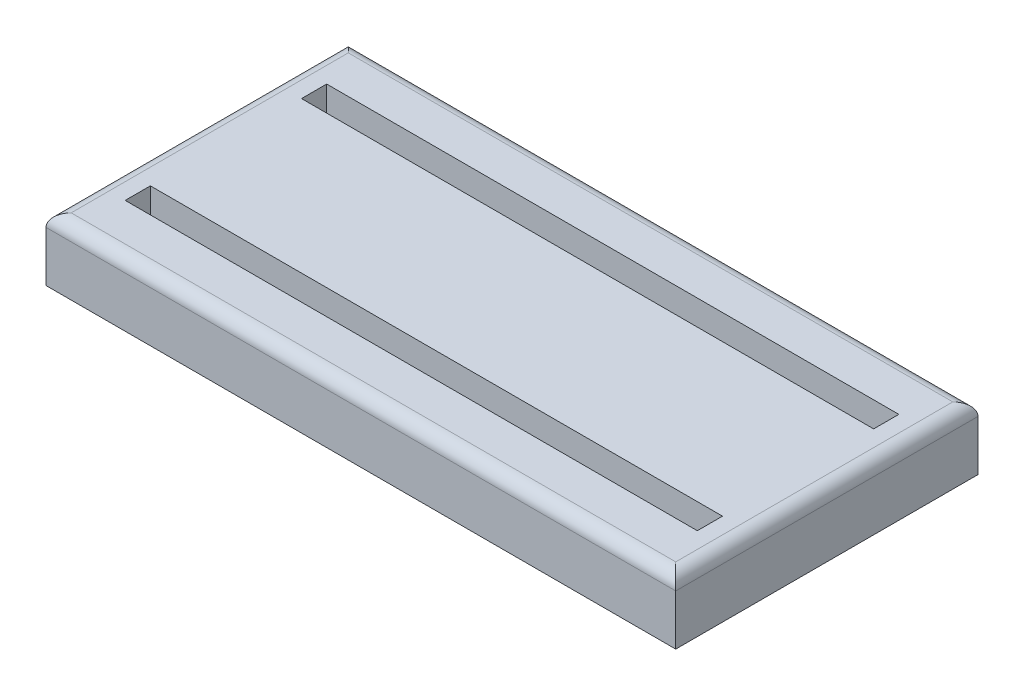
SolidWorks part; units mm, degrees
ref_plane "Front Plane" through (0, 0, 0) normal (0, 0, 1) x (1, 0, 0)
ref_plane "Top Plane" through (0, 0, 0) normal (0, 1, 0) x (1, 0, 0)
ref_plane "Right Plane" through (0, 0, 0) normal (1, 0, 0) x (0, 0, -1)
sketch "Sketch2" plane through (0, 0, 0) normal (0, 1, 0) x (1, 0, 0)
  line L0 (0, 242.4303) -> (0, -237.7501) construction
  line L1 (-63.5, 17.78) -> (-63.5, -43.18)
  line L2 (-63.5, 17.78) -> (63.5, 17.78)
  line L3 (-63.5, -43.18) -> (63.5, -43.18)
  line L4 (63.5, 17.78) -> (63.5, -43.18)
  dimension "D1" = 127
  dimension "D2" = 63.5
  dimension "D3" = 60.96
  dimension "D4" = 43.18
extrude "Boss-Extrude1" add sketch "Sketch2" along normal blind 12.7
fillet "Fillet1" radius 2.54 4 edges at (63.5, 12.7, 12.7) (-63.5, 12.7, 12.7) (0, 12.7, 43.18) (0, 12.7, -17.78)
sketch "Sketch3" plane through (0, 12.7, 0) normal (0, 1, 0) x (1, 0, 0)
  line L0 (57.6928, 2.54) -> (57.6928, 7.62)
  line L1 (57.6928, 2.54) -> (-57.6928, 2.54)
  line L2 (57.6928, 7.62) -> (-57.6928, 7.62)
  line L3 (-57.6928, 2.54) -> (-57.6928, 7.62)
  line L5 (63.5, 17.78) -> (63.5, -43.18) construction
  line L6 (-63.5, 17.78) -> (63.5, 17.78) construction
  line L7 (-60.96, -12.7) -> (60.96, -12.7) construction
  line L8 (-60.96, 15.24) -> (-60.96, -40.64) construction
  line L9 (60.96, -40.64) -> (60.96, 15.24) construction
  line L10 (57.6928, -27.94) -> (57.6928, -33.02)
  line L11 (57.6928, -33.02) -> (-57.6928, -33.02)
  line L12 (-57.6928, -27.94) -> (-57.6928, -33.02)
  line L13 (57.6928, -27.94) -> (-57.6928, -27.94)
  dimension "D1" = 115.3856
  dimension "D2" = 5.8072
  dimension "D3" = 10.16
  dimension "D4" = 5.08
extrude "Cut-Extrude1" cut sketch "Sketch3" against normal blind 12.7
